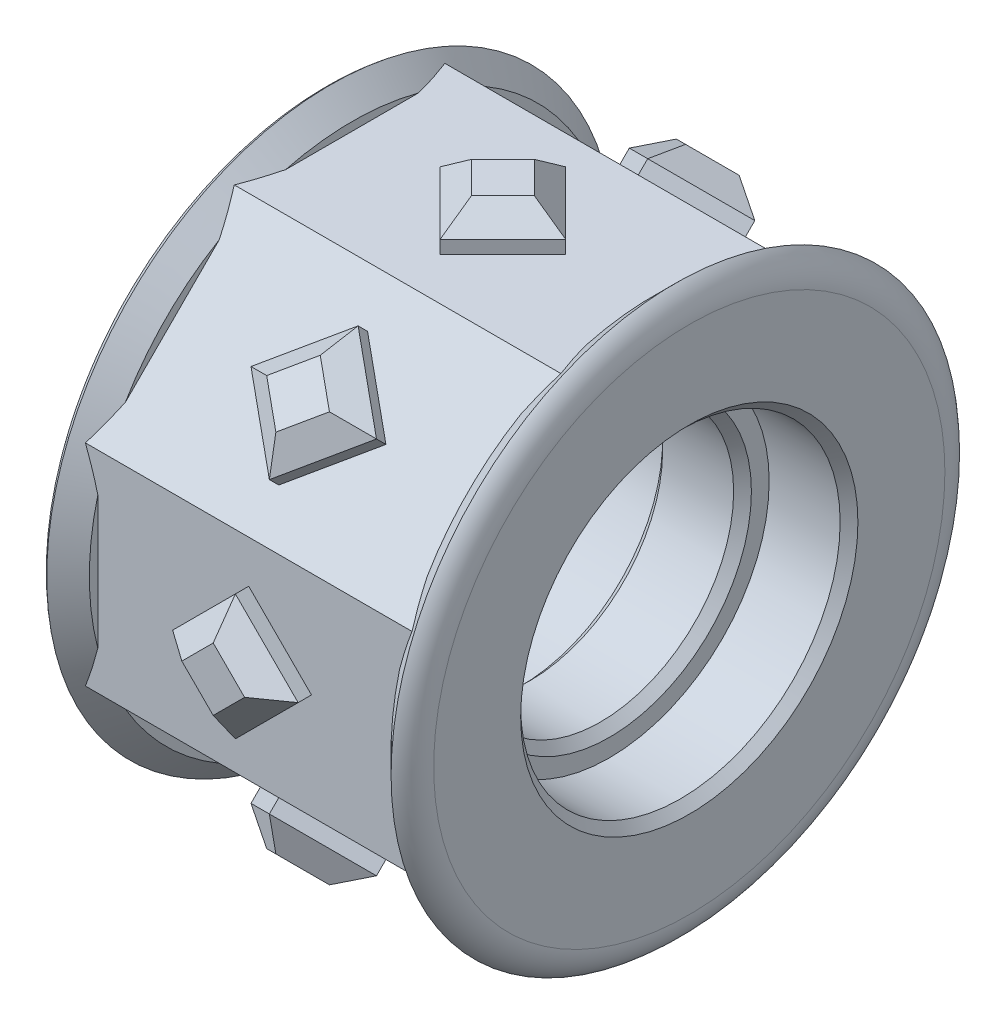
SolidWorks part; units mm, degrees
ref_plane "Front Plane" through (0, 0, 0) normal (0, 0, 1) x (1, 0, 0)
ref_plane "Top Plane" through (0, 0, 0) normal (0, 1, 0) x (1, 0, 0)
ref_plane "Right Plane" through (0, 0, 0) normal (1, 0, 0) x (0, 0, -1)
sketch "Sketch1" plane through (0, 0, 0) normal (1, 0, 0) x (0, 0, -1)
  line L0 (0, 0) -> (15.7785, 0) construction
  line L5 (0, 0) -> (0, 50.7444) construction
  line L7 (14.3201, 5.9316) -> (5.9316, 14.3201)
  line L8 (5.9316, 14.3201) -> (-5.9316, 14.3201)
  line L9 (-5.9316, 14.3201) -> (-14.3201, 5.9316)
  line L10 (-14.3201, 5.9316) -> (-14.3201, -5.9316)
  line L11 (-14.3201, -5.9316) -> (-5.9316, -14.3201)
  line L12 (-5.9316, -14.3201) -> (5.9316, -14.3201)
  line L13 (5.9316, -14.3201) -> (14.3201, -5.9316)
  line L14 (14.3201, -5.9316) -> (14.3201, 5.9316)
  circle A2 centre (0, 0) radius 15.5 construction
sketch "Sketch3" plane through (0, 0, 0) normal (1, 0, 0) x (0, 0, -1)
  circle A0 centre (0, 0) radius 16
extrude "Торец" add sketch "Sketch3" along normal blind 2 separate body
extrude "Барабан" add sketch "Sketch1" along normal blind 21
chamfer "Chamfer1" distance 1.2 angle 45 1 edges at (2, 0, -16)
fillet "Fillet1" radius 2 1 edges at (0, 0, -16)
sketch "Sketch8" plane through (21, 0, 0) normal (1, 0, 0) x (0, 0, -1)
  circle A0 centre (0, 0) radius 16
extrude "Торец внутр" add sketch "Sketch8" against normal blind 2
chamfer "Chamfer2" distance 1.2 angle 45 1 edges at (19, 0, -16)
fillet "Fillet2" radius 2 1 edges at (21, 0, -16)
sketch "Sketch4" plane through (21, 0, 0) normal (1, 0, 0) x (0, 0, -1)
  circle A0 centre (0, 0) radius 9
  dimension "D1" = 18
extrude "Посадка под подшипник" cut sketch "Sketch4" against normal blind 4.5
sketch "Sketch5" plane through (16.5, 0, 0) normal (1, 0, 0) x (0, 0, -1)
  circle A0 centre (0, 0) radius 7.5
  dimension "D1" = 15
extrude "Cut-Extrude2" cut sketch "Sketch5" against normal through all
sketch "Sketch6" plane through (0, 0, 0) normal (-1, 0, 0) x (0, 0, 1)
  circle A0 centre (0, 0) radius 13
extrude "Cut-Extrude3" cut sketch "Sketch6" against normal blind 5
sketch "Sketch10" plane through (5, 0, 0) normal (-1, 0, 0) x (0, 0, 1)
  circle A0 centre (0, 0) radius 9
  dimension "D1" = 18
extrude "Посадка под подшипник нар" cut sketch "Sketch10" against normal blind 6.5
chamfer "Chamfer5" distance 0.5 angle 45 2 edges at (11.5, 0, 7.5) (16.5, 0, -7.5)
chamfer "Chamfer6" distance 0.5 angle 45 2 edges at (5, 0, 9) (21, 0, -9)
chamfer "Chamfer7" distance 1.2 angle 45 1 edges at (0, 0, 13)
sketch "Sketch11" plane through (0, 10.1259, 10.1259) normal (0, 0.7071, 0.7071) x (1, 0, 0)
  line L0 (10.5, 7.8328) -> (10.5, -8.4714) construction
  line L1 (-2.5033, 0) -> (25.1868, 0) construction
  line L3 (10.5, -3.5355) -> (14.0355, 0)
  line L4 (10.5, -3.5355) -> (6.9645, 0)
  line L5 (6.9645, 0) -> (10.5, 3.5355)
  line L6 (14.0355, 0) -> (10.5, 3.5355)
  line L7 (10.5, -3.5355) -> (10.5, 3.5355) construction
  line L8 (6.9645, 0) -> (14.0355, 0) construction
  point P5 (10.5, 0)
  dimension "D1" = 5
  dimension "D2" = 5
extrude "Boss-Extrude1" add sketch "Sketch11" along normal blind 2
chamfer "Chamfer8" distance 1.25 angle 45 4 edges at (12.2678, 10.2901, 12.7901) (12.2678, 12.7901, 10.2901) (8.7322, 12.7901, 10.2901) (8.7322, 10.2901, 12.7901)
pattern_circular "CirPattern1" count 8 over 360 about axis through (20.2, 0, 0) along (1, 0, 0) of "Boss-Extrude1", "Chamfer8"
sketch "Sketch12" plane through (5, 0, 0) normal (-1, 0, 0) x (0, 0, 1)
  circle A0 centre (0, 11) radius 1.25
  dimension "D2" = 2.5
  dimension "D1" = 11
extrude "Cut-Extrude4" [suppressed] cut sketch "Sketch12" against normal blind 5
pattern_circular "CirPattern2" [suppressed] count 4 over 360 of bodies 113
sketch "Sketch13" plane through (5, 0, 0) normal (1, 0, 0) x (0, 0, -1)
  line L0 (-1.9868, 10.9366) -> (-1.5534, 8.758)
  line L1 (0, 0) -> (0, 16.1318) construction
  line L2 (-1.7906, 10.9756) -> (-1.3573, 8.797) construction
  line L3 (1.7906, 10.9756) -> (1.3573, 8.797) construction
  line L4 (1.9868, 10.9366) -> (1.5534, 8.758)
  arc A0 (0.8821, 12.1681) -> (-0.8821, 12.1681) centre (0, 0) ccw construction
  arc A1 (1.7906, 10.9756) -> (0.8821, 12.1681) centre (0.8098, 11.1707) ccw construction
  arc A2 (-0.8821, 12.1681) -> (-1.7906, 10.9756) centre (-0.8098, 11.1707) ccw construction
  arc A3 (0.3347, 7.993) -> (-0.3347, 7.993) centre (0, 0) ccw construction
  arc A4 (1.3573, 8.797) -> (0.3347, 7.993) centre (0.3765, 8.9921) cw construction
  arc A5 (-1.3573, 8.797) -> (-0.3347, 7.993) centre (-0.3765, 8.9921) ccw construction
  arc A6 (0.8966, 12.3675) -> (-0.8966, 12.3675) centre (0, 0) ccw
  arc A7 (-0.8966, 12.3675) -> (-1.9868, 10.9366) centre (-0.8098, 11.1707) ccw
  arc A8 (-1.5534, 8.758) -> (-0.3263, 7.7932) centre (-0.3765, 8.9921) ccw
  arc A9 (0.3263, 7.7932) -> (-0.3263, 7.7932) centre (0, 0) ccw
  arc A10 (1.5534, 8.758) -> (0.3263, 7.7932) centre (0.3765, 8.9921) cw
  arc A11 (1.9868, 10.9366) -> (0.8966, 12.3675) centre (0.8098, 11.1707) ccw
  dimension "D1" = 1
  dimension "D2" = 1
  dimension "D3" = 0.2
extrude "Cut-Extrude8" cut sketch "Sketch13" along normal blind 3
pattern_circular "CirPattern3" count 4 over 360 about axis through (1.2, 0, 0) along (-1, 0, 0) of "Cut-Extrude8"
